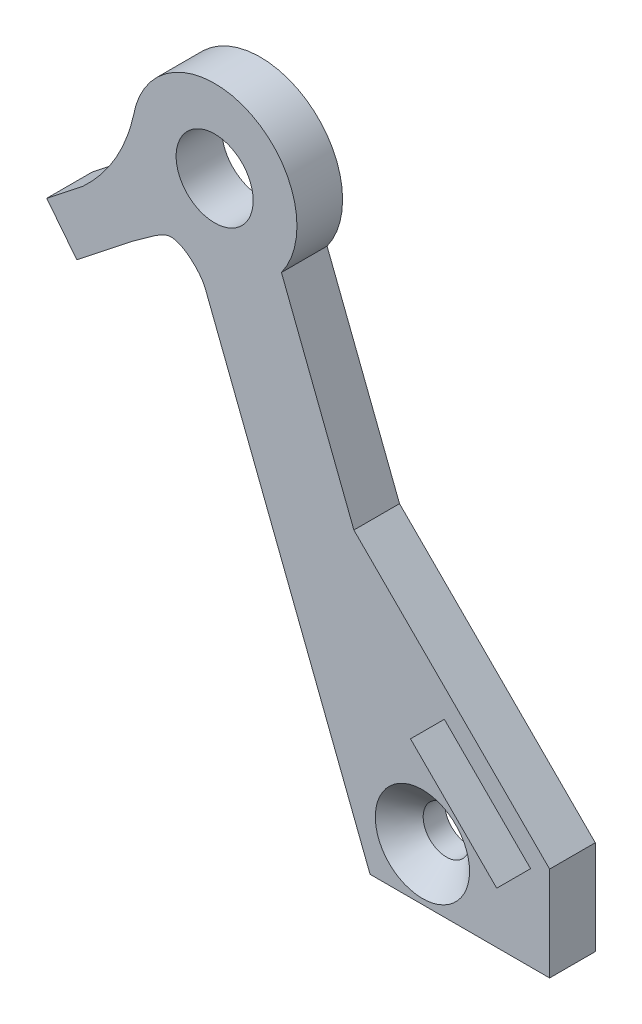
SolidWorks part; units mm, degrees
ref_plane "Front Plane" through (0, 0, 0) normal (0, 0, 1) x (1, 0, 0)
ref_plane "Top Plane" through (0, 0, 0) normal (0, 1, 0) x (1, 0, 0)
ref_plane "Right Plane" through (0, 0, 0) normal (1, 0, 0) x (0, 0, -1)
sketch "Sketch1" plane through (0, 0, 0) normal (0, 0, 1) x (1, 0, 0)
  line L0 (0, 12) -> (12, 0) construction
  line L1 (0, 0) -> (12, 0)
  line L2 (0, 0) -> (0, 12) construction
  line L3 (0, 12) -> (12, 12) construction
  line L4 (12, 0) -> (12, 12) construction
  line L5 (0, 0) -> (3.5, 0)
  line L6 (0, 0) -> (0, 3.5)
  line L7 (0, 3.5) -> (3.5, 3.5) construction
  line L8 (3.5, 0) -> (3.5, 3.5) construction
  line L9 (8.2662, 3.6278) -> (8.3192, 3.6808) construction
  line L10 (8.4645, 3.4295) -> (2.7015, 9.1924)
  line L11 (2.7015, 9.1924) -> (4.9643, 11.4551)
  line L12 (8.4645, 3.4295) -> (10.7272, 5.6922)
  line L13 (4.9643, 11.4551) -> (10.7272, 5.6922)
  line L14 (0, 0) -> (-13.1831, 33.9987)
  line L15 (-13.1831, 33.9987) -> (-7.5889, 36.1679)
  line L16 (-7.5889, 36.1679) -> (-1.0815, 19.3854)
  line L17 (-1.0815, 19.3854) -> (12, 6.3039)
  line L18 (12, 0) -> (8.5175, 3.4825)
  line L19 (12, 6.3039) -> (12, 0)
  line L20 (0, 0) -> (0, 40.9886) construction
  line L21 (-10.386, 35.0833) -> (-20.603, 27.0451) construction
  line L22 (-19.5982, 25.768) -> (-21.6078, 28.3222)
  line L23 (-21.6078, 28.3222) -> (-15.5204, 33.1115) construction
  line L24 (-19.5982, 25.768) -> (-13.5109, 30.5572)
  line L25 (-21.6078, 28.3222) -> (-19.2059, 30.2119)
  line L26 (-15.7957, 36.0761) -> (-10.386, 35.0833) construction
  circle A0 centre (3.5, 3.5) radius 1.5
  circle A1 centre (-10.386, 35.0833) radius 2.575
  circle A3 centre (-10.386, 35.0833) radius 5.5
  spline S0 degree 2 poles (-19.2059, 30.2119) (-16.562, 32.6551) (-15.7957, 36.0761) knots 0 0 0 1 1 1
  spline S1 degree 3 poles (-15.802, 28.7547) (-14.2507, 29.8327) (-13.2685, 30.9342) (-11.3126, 29.1304) (-11.0236, 28.4294) knots 0 0 0 0 0.517104 1 1 1 1
  point P28 (-20.603, 27.0451)
  point P32 (-12.1806, 29.8481)
  dimension "D5" = 3
  dimension "D6" = 5.15
  dimension "D7" = 11
  dimension "D26" = 6.892
  dimension "D1" = 12
  dimension "D2" = 12
  dimension "D3" = 3.5
  dimension "D4" = 3.5
  dimension "D8" = 45
  dimension "D9" = 6.3039
  dimension "D10" = 90
  dimension "D11" = 90
  dimension "D12" = 18
  dimension "D13" = 18.5
  dimension "D14" = 3.2
  dimension "D15" = 8.15
  dimension "D16" = 0.075
  dimension "D17" = 4.925
  dimension "D18" = 6
  dimension "D19" = 90
  dimension "D20" = 3.25
  dimension "D21" = 90
  dimension "D22" = 90
  dimension "D23" = 13
  dimension "D24" = 73
  dimension "D25" = 3.0562
  dimension "D27" = 31.593
extrude "Boss-Extrude1" add sketch "Sketch1" along normal blind 3.05 contours A3 S1 L14 L15 A1 L16 S0 | L14 A3 L16 L15 A1 | A3 L14 L1 L12 L10 L11 L13 L19 L17 L16 A0 | S0 L25 L22 L24 A3 | L24 S1 A3 | A3 S1 L14 region at (-0.3108, 13.3452, 0) region at (-11.6618, 29.4634, 0) region at (-12.0582, 30.0064, 0) region at (-9.1668, 31.9391, 0) region at (-13.9332, 30.058, 0) region at (-17.5126, 29.7891, 0)
hole_wizard "CSK for M3 Flat Head Machine Screw1" positions "Sketch2" profile "Sketch3" countersink size "M3" standard "ANSI Metric" end condition through all
sketch "Sketch2" plane through (0, 0, 3.05) normal (0, 0, 1) x (1, 0, 0)
  point P0 (3.5, 3.5)
sketch "Sketch3" plane through (3.5, 3.5, 3.05) normal (1, 0, 0) x (0, -1, 0)
  line L0 (0, 0) -> (0, 3.05)
  line L1 (0, 3.05) -> (1.55, 3.05)
  line L2 (1.55, 3.05) -> (1.55, 1.6)
  line L3 (1.55, 1.6) -> (3.15, 0)
  line L5 (3.15, 0) -> (0, 0)
  line L6 (-1.55, 1.6) -> (-3.15, 0) construction
  line L11 (0, -6.35) -> (0, 107.95) construction
  dimension "Thru Hole Dia." = 3.1
  dimension "Thru Hole Depth" = 3.05
  dimension "Near C'Sink Dia." = 6.3
  dimension "Near C'Sink Angle" = 90
